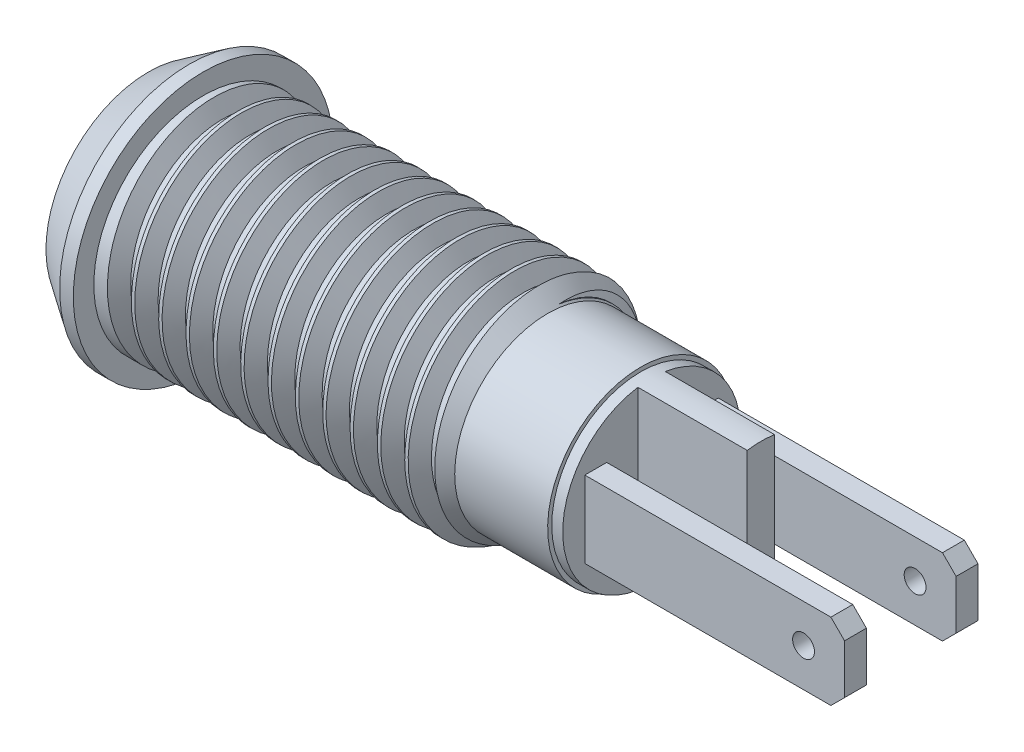
SolidWorks part; units mm, degrees
ref_plane "Front Plane" through (0, 0, 0) normal (0, 0, 1) x (1, 0, 0)
ref_plane "Top Plane" through (0, 0, 0) normal (0, 1, 0) x (1, 0, 0)
ref_plane "Right Plane" through (0, 0, 0) normal (1, 0, 0) x (0, 0, -1)
sketch "Sketch1" plane through (0, 0, 0) normal (0, 0, 1) x (1, 0, 0)
  line L0 (0, 0) -> (-17.9, 0) construction
  line L1 (-17.9, 0) -> (-17.9, 3.05)
  line L2 (-17.9, 3.05) -> (-17.4, 3.55)
  line L3 (-18, 3.75) -> (-18, 3.55)
  line L4 (-18, 3.75) -> (-16.5, 4.75)
  line L5 (0, 0) -> (-17.9, 0)
  line L6 (-16, 4) -> (-4, 4)
  line L7 (0, 3.4) -> (0, 0)
  line L8 (-16.5, 4.75) -> (-16, 4.75)
  line L9 (-16, 4.75) -> (-16, 4)
  line L10 (-18, 3.55) -> (-17.4, 3.55)
  line L11 (0, 3.4) -> (-3.4, 3.4)
  line L12 (-3.4, 3.4) -> (-4, 4)
  dimension "D1" = 4
  dimension "D2" = 1.5
  dimension "D3" = 0.6
  dimension "D4" = 1
  dimension "D5" = 16
  dimension "D6" = 0.5
  dimension "D7" = 0.2
  dimension "D8" = 0.5
  dimension "D9" = 4.75
  dimension "D10" = 45
  dimension "D11" = 3.4
  dimension "D12" = 12
  dimension "D13" = 45
revolve "Revolve1" add sketch "Sketch1" angle 360 about L0
thread "Thread1" pitch 1 method cut profile "Thread Profile1" start angle 0, offset 0, length 14, pitch 1, diameter 8
ref_plane "Plane1" through (-16, 0, -4) normal (0, -1, 0) x (0, 0, -1)
sketch "Thread Profile1" plane through (-16, 0, -4) normal (0, -1, 0) x (0, 0, -1)
  line L0 (0, 0) -> (0, 1) construction
  line L11 (0, 0) -> (0, 0.875)
  line L12 (0, 0.875) -> (-0.5413, 0.5625)
  line L13 (-0.5413, 0.5625) -> (-0.5413, 0.3125)
  line L15 (-0.5413, 0.3125) -> (0, 0)
  line L17 (-0.5413, 0.4375) -> (0, 0.4375) construction
  point P2 (0, 0)
  dimension "Pitch" = 1
  dimension "Profile_Angle" = 60
  dimension "Profile_Land" = 0.25
  dimension "Profile_Height" = 0.5413
sketch "Sketch5" plane through (0, 0, 0) normal (1, 0, 0) x (0, 0, -1)
  circle A0 centre (0, 0) radius 3.25
  dimension "D1" = 6.5
extrude "Boss-Extrude1" add sketch "Sketch5" along normal blind 0.4
sketch "Sketch6" plane through (0.4, 0, 0) normal (1, 0, 0) x (0, 0, -1)
  line L2 (-0.5, -3.2113) -> (-0.5, 3.2113)
  line L4 (0.5, -3.2113) -> (0.5, 3.2113)
  line L5 (-0.5, -3.2113) -> (0.5, 3.2113) construction
  line L6 (-0.5, 3.2113) -> (0.5, -3.2113) construction
  circle A0 centre (0, 0) radius 3.25 construction
  arc A1 (0.5, 3.2113) -> (-0.5, 3.2113) centre (0, 0) ccw
  arc A2 (-0.5, -3.2113) -> (0.5, -3.2113) centre (0, 0) ccw
  point P0 (0, 0)
  dimension "D1" = 1
extrude "Boss-Extrude2" add sketch "Sketch6" along normal blind 4
sketch "Sketch7" plane through (0.4, 0, 0) normal (1, 0, 0) x (0, 0, -1)
  line L0 (-2.0404, 0) -> (2.0404, 0) construction
  line L2 (2.4404, -1.4) -> (1.6404, -1.4)
  line L3 (2.4404, -1.4) -> (2.4404, 1.4)
  line L4 (2.4404, 1.4) -> (1.6404, 1.4)
  line L5 (1.6404, -1.4) -> (1.6404, 1.4)
  line L6 (2.4404, -1.4) -> (1.6404, 1.4) construction
  line L7 (2.4404, 1.4) -> (1.6404, -1.4) construction
  line L8 (-2.4404, -1.4) -> (-1.6404, -1.4)
  line L9 (-2.4404, -1.4) -> (-2.4404, 1.4)
  line L10 (-2.4404, 1.4) -> (-1.6404, 1.4)
  line L11 (-1.6404, -1.4) -> (-1.6404, 1.4)
  line L12 (-2.4404, -1.4) -> (-1.6404, 1.4) construction
  line L13 (-2.4404, 1.4) -> (-1.6404, -1.4) construction
  dimension "D1" = 2.8
  dimension "D2" = 0.8
extrude "Boss-Extrude3" add sketch "Sketch7" along normal blind 9.5
chamfer "Chamfer1" distance 0.5 angle 45 4 edges at (9.9, -1.4, 2.0404) (9.9, 1.4, 2.0404) (9.9, -1.4, -2.0404) (9.9, 1.4, -2.0404)
sketch "Sketch8" plane through (0, 0, 2.4404) normal (0, 0, 1) x (1, 0, 0)
  line L0 (9.9, 0) -> (8.4, 0) construction
  line L1 (9.9, 0.9) -> (9.9, -0.9) construction
  circle A0 centre (8.4, 0) radius 0.4
  dimension "D1" = 0.8
  dimension "D2" = 1.5
extrude "Cut-Extrude1" cut sketch "Sketch8" against normal through all
